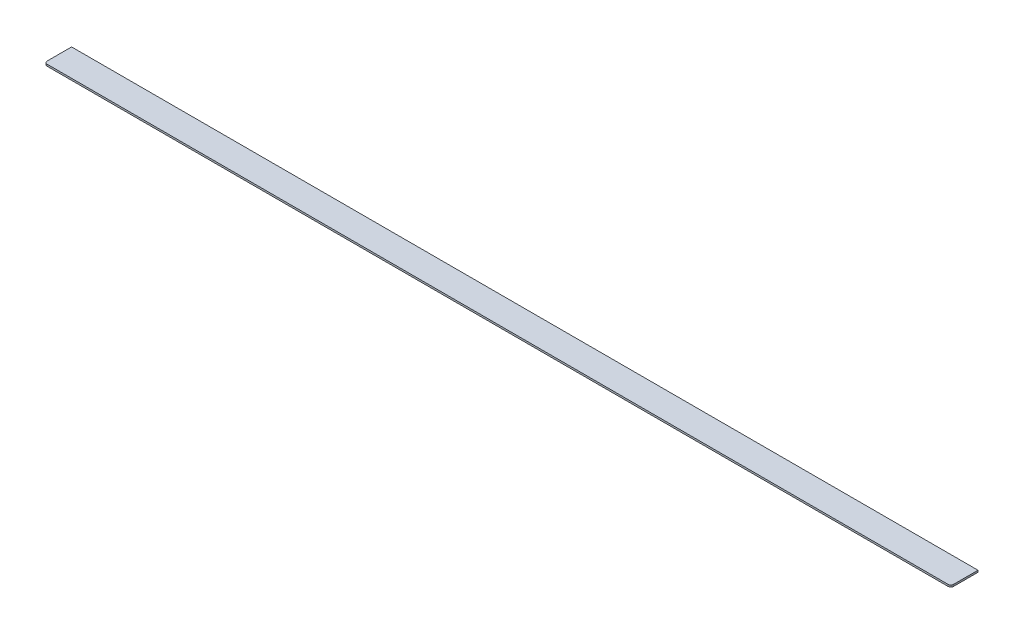
SolidWorks part; units mm, degrees
ref_plane "Спереди" through (0, 0, 0) normal (0, 0, 1) x (1, 0, 0)
ref_plane "Сверху" through (0, 0, 0) normal (0, 1, 0) x (1, 0, 0)
ref_plane "Справа" through (0, 0, 0) normal (1, 0, 0) x (0, 0, -1)
sketch "Эскиз1" plane through (0, 0, 0) normal (0, 1, 0) x (1, 0, 0)
  line L1 (3, 0) -> (997, 0)
  line L2 (0, 3) -> (0, 30)
  line L3 (0, 30) -> (1000, 30)
  line L4 (1000, 3) -> (1000, 30)
  arc A0 (3, 0) -> (0, 3) centre (3, 3) cw
  arc A1 (997, 0) -> (1000, 3) centre (997, 3) ccw
  point P7 (0, 0)
  point P10 (1000, 0)
  dimension "D3" = 3
  dimension "D4" = 3
  dimension "D1" = 30
  dimension "D2" = 1000
base flange "Базовая кромка1" sketch "Эскиз1" thickness 2 reverse thickness direction no parameters "D1"=1
sketch "Сгиб-Линии1" [suppressed] plane through (0, 0, 0) normal (0, 1, 0) x (1, 0, 0)
sketch "Граничная рамка1" [suppressed] plane through (0, 0, 0) normal (0, 1, 0) x (1, 0, 0)
sheet metal parameters "Листовой металл1" thickness 2 parameters "D1"=1
flat pattern "Развертка1" [suppressed]
sketch "Сгиб-Линии2" plane through (0, 0, 0) normal (0, 1, 0) x (1, 0, 0)
sketch3d "Граничная рамка2" [suppressed]
  line L0 (997, 27, 0) -> (-3, 27, 0) construction
  line L1 (997, -3, 0) -> (-3, -3, 0) construction
  line L2 (997, 27, 0) -> (997, -3, 0) construction
  line L3 (-3, 27, 0) -> (-3, -3, 0) construction
